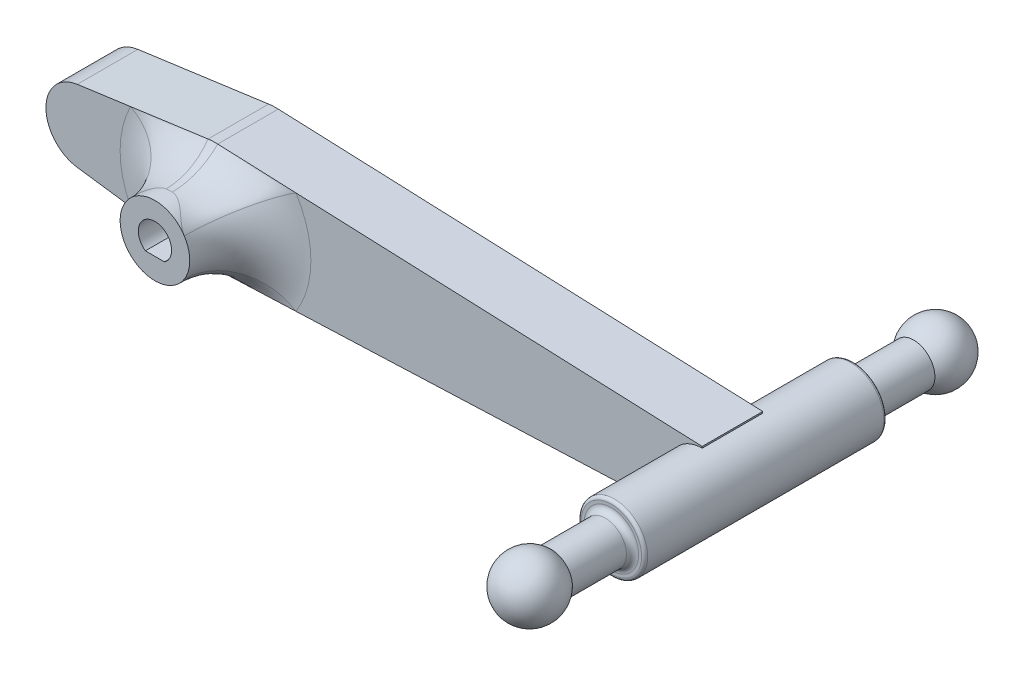
SolidWorks part; units mm, degrees
ref_plane "Front Plane" through (0, 0, 0) normal (0, 0, 1) x (1, 0, 0)
ref_plane "Top Plane" through (0, 0, 0) normal (0, 1, 0) x (1, 0, 0)
ref_plane "Right Plane" through (0, 0, 0) normal (1, 0, 0) x (0, 0, -1)
sketch "Sketch2" plane through (0, 0, 0) normal (0, 0, 1) x (1, 0, 0)
  line L0 (80.3645, 0) -> (-42.1921, 0) construction
  line L1 (-22.8182, -5.944) -> (-1.2273, -8.9159)
  line L2 (0.3645, -8.9926) -> (80.3645, -5.75)
  line L3 (80.3645, -5.75) -> (80.3645, 5.75)
  line L4 (0, 24.5757) -> (0, -40.5685) construction
  line L5 (-22.8182, 5.944) -> (-1.2273, 8.9159)
  line L6 (0.3645, 8.9926) -> (80.3645, 5.75)
  line L7 (-1.5811, -2.25) -> (1.5811, -2.25)
  arc A0 (-22.8182, 5.944) -> (-22.8182, -5.944) centre (-22, 0) ccw
  arc A1 (-1.2273, -8.9159) -> (0.3645, -8.9926) centre (0, 0) ccw
  arc A2 (-1.2273, 8.9159) -> (0.3645, 8.9926) centre (0, 0) cw
  arc A3 (1.5811, -2.25) -> (-1.5811, -2.25) centre (0, 0) ccw
  point P14 (0, 2.75)
  dimension "D1" = 6
  dimension "D7" = 9
  dimension "D5" = 2.75
  dimension "D2" = 22
  dimension "D3" = 80
  dimension "D4" = 5
  dimension "D6" = 5.75
extrude "Boss-Extrude2" add sketch "Sketch2" along normal mid plane 10
sketch "Sketch3" plane through (80.3645, 0, 0) normal (1, 0, 0) x (0, 0, -1)
  line L0 (33.5, 0) -> (-33.5, 0) construction
  line L1 (-33.5, 0) -> (-33.5, 3.5)
  line L2 (-33.5, 3.5) -> (-21, 3.5)
  line L3 (-20, 4.5) -> (-20, 5)
  line L4 (-19.5, 5.5) -> (19.5, 5.5)
  line L5 (20, 5) -> (20, 4.5)
  line L6 (21, 3.5) -> (33.5, 3.5)
  line L7 (33.5, 3.5) -> (33.5, 0)
  line L8 (33.5, 0) -> (-33.5, 0)
  arc A0 (-21, 3.5) -> (-20, 4.5) centre (-21, 4.5) ccw
  arc A1 (20, 4.5) -> (21, 3.5) centre (21, 4.5) ccw
  arc A2 (-20, 5) -> (-19.5, 5.5) centre (-19.5, 5) cw
  arc A3 (19.5, 5.5) -> (20, 5) centre (19.5, 5) cw
  point P12 (20, 4.75)
  point P13 (0, 5.5)
  point P17 (-20, 5.5)
  point P20 (20, 5.5)
  dimension "D7" = 1
  dimension "D8" = 1
  dimension "D9" = 0.5
  dimension "D10" = 0.5
  dimension "D1" = 40
  dimension "D2" = 13.5
  dimension "D3" = 13.5
  dimension "D4" = 3.5
  dimension "D5" = 5.5
  dimension "D6" = 3.5
revolve "Revolve12" add sketch "Sketch3" angle 360 about L0
sketch "Sketch5" plane through (0, 0, -33.5) normal (0, 0, -1) x (-1, 0, 0)
  line L0 (-80.3645, 5) -> (-80.3645, -5) construction
  line L1 (-80.3645, 5) -> (-80.3645, -5)
  circle A0 centre (-80.3645, 0) radius 5 construction
  arc A1 (-80.3645, 5) -> (-80.3645, -5) centre (-80.3645, 0) ccw
revolve "Revolve16" add sketch "Sketch5" angle 360 about L0
sketch "Sketch6" plane through (0, 0, 33.5) normal (0, 0, 1) x (1, 0, 0)
  line L0 (80.3645, 5) -> (80.3645, -5) construction
  line L1 (80.3645, 5) -> (80.3645, -5)
  circle A0 centre (80.3645, 0) radius 5 construction
  arc A1 (80.3645, 5) -> (80.3645, -5) centre (80.3645, 0) ccw
revolve "Revolve17" add sketch "Sketch6" angle 360 about L0
sketch "Sketch8" plane through (0, 0, 5) normal (0, 0, 1) x (1, 0, 0)
  line L0 (-1.5811, -2.25) -> (1.5811, -2.25)
  circle A0 centre (0, 0) radius 5.75
  arc A1 (1.5811, -2.25) -> (-1.5811, -2.25) centre (0, 0) ccw
  point P6 (0, 2.75)
  dimension "D1" = 2.75
  dimension "D2" = 3
  dimension "D3" = 5
extrude "Boss-Extrude5" add sketch "Sketch8" along normal mid plane 20
fillet "Fillet1" radius 10 1 edges at (5.75, 0, 5)
sketch "Sketch9" plane through (0, -2.25, 0) normal (0, 1, 0) x (1, 0, 0)
  line L0 (0, -15) -> (0, -10.315) construction
  line L1 (-1.5811, -15) -> (1.5811, -15) construction
  circle A0 centre (0, -11) radius 1.5
  dimension "D1" = 3
  dimension "D2" = 4
sketch "Sketch10" plane through (0, 0, 5) normal (0, 0, 1) x (1, 0, 0)
  line L1 (12.8788, 16.4309) -> (97.7507, 16.4309)
  line L2 (12.8788, 16.4309) -> (12.8788, -17.9161)
  line L3 (12.8788, -17.9161) -> (97.7507, -17.9161)
  line L4 (97.7507, 16.4309) -> (97.7507, -17.9161)
sketch "Sketch11" plane through (0, 0, 5) normal (0, 0, 1) x (1, 0, 0)
  line L1 (-9.9064, 12.4494) -> (-35.5409, 12.4494)
  line L2 (-9.9064, 12.4494) -> (-9.9064, -9.8047)
  line L3 (-9.9064, -9.8047) -> (-35.5409, -9.8047)
  line L4 (-35.5409, 12.4494) -> (-35.5409, -9.8047)
